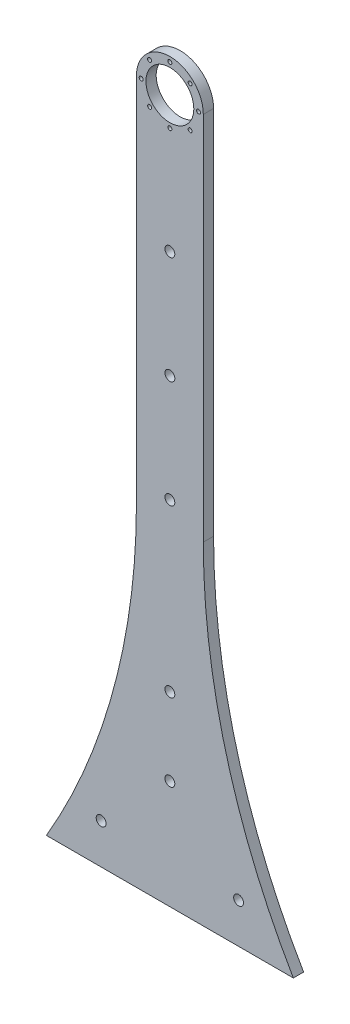
SolidWorks part; units mm, degrees
ref_plane "Front Plane" through (0, 0, 0) normal (0, 0, 1) x (1, 0, 0)
ref_plane "Top Plane" through (0, 0, 0) normal (0, 1, 0) x (1, 0, 0)
ref_plane "Right Plane" through (0, 0, 0) normal (1, 0, 0) x (0, 0, -1)
sketch "Sketch1" plane through (0, 0, 0) normal (0, 0, 1) x (1, 0, 0)
  line L0 (-112.3, 0) -> (112.3, 0) construction
  line L1 (-112.3, 0) -> (112.3, 0)
  line L2 (-29, 408.6) -> (29, 408.6) construction
  line L3 (-29, 408.6) -> (29, 408.6)
  line L4 (-31, 371.4) -> (-31, 408.6) construction
  line L5 (31, 408.6) -> (31, 371.4) construction
  line L6 (-31, 371.4) -> (-31, 408.6)
  line L7 (31, 408.6) -> (31, 371.4)
  line L8 (58.8, 370.05) -> (-58.8, 370.05) construction
  line L9 (58.8, 370.05) -> (-58.8, 370.05)
  line L10 (-125, 20) -> (125, 20) construction
  line L11 (-125, 20) -> (125, 20)
  line L12 (125, 0) -> (125, 10.5) construction
  line L13 (125, 0) -> (125, 10.5)
  line L14 (-125, 10.5) -> (-125, 0) construction
  line L15 (-125, 10.5) -> (-125, 0)
  circle A1 centre (0, 390) radius 8.5
  circle A2 centre (0, 390) radius 8.5
  circle A3 centre (0, 390) radius 3.025
  circle A4 centre (0, 390) radius 3.025
  dimension "D1" = 0
  dimension "D2" = 0
sketch "Sketch2" plane through (0, 0, 0) normal (0, 0, 1) x (1, 0, 0)
  line L0 (-29, 408.6) -> (29, 408.6) construction
  line L1 (-17.6, 390) -> (-17.6, 0) construction
  line L2 (-112.3, 0) -> (112.3, 0) construction
  line L3 (17.6, 390) -> (17.6, 0) construction
  line L4 (-65, 0) -> (65, 0) construction
  line L5 (-65, 0) -> (-65, 20) construction
  line L6 (-125, 20) -> (125, 20) construction
  line L7 (65, 0) -> (65, 20) construction
  line L8 (-125, 10.5) -> (-125, 0) construction
  line L9 (-17.6, 390) -> (-17.6, 195)
  line L10 (17.6, 390) -> (17.6, 195)
  line L11 (-65, 20) -> (65, 20)
  arc A0 (17.6, 390) -> (-17.6, 390) centre (0, 390) ccw
  circle A3 centre (0, 390) radius 12.6
  arc A4 (17.6, 195) -> (65, 20) centre (364.3485, 195) ccw
  arc A5 (-65, 20) -> (-17.6, 195) centre (-364.3485, 195) ccw
  point P3 (0, 407.6)
  point P13 (0, 0)
  point P30 (17.6, 195)
  dimension "D2" = 5
  dimension "D1" = 1
  dimension "D3" = 60
extrude "Boss-Extrude1" add sketch "Sketch2" against normal blind 5.4
sketch "Sketch3" plane through (0, 0, -5.4) normal (0, 0, -1) x (-1, 0, 0)
  line L0 (0, 407.6) -> (0, 402.6) construction
  arc A0 (17.6, 390) -> (-17.6, 390) centre (0, 390) ccw construction
  circle A1 centre (0, 390) radius 12.6 construction
  circle A2 centre (0, 405.1) radius 1.05
  circle A3 centre (10.6773, 400.6773) radius 1.05
  circle A4 centre (15.1, 390) radius 1.05
  circle A5 centre (10.6773, 379.3227) radius 1.05
  circle A6 centre (0, 374.9) radius 1.05
  circle A7 centre (-10.6773, 379.3227) radius 1.05
  circle A8 centre (-15.1, 390) radius 1.05
  circle A9 centre (-10.6773, 400.6773) radius 1.05
  circle A10 centre (0, 318.7) radius 2.1 construction
  circle A11 centre (0, 318.7) radius 2.1 construction
  circle A12 centre (0, 262.1) radius 2.1 construction
  circle A13 centre (0, 262.1) radius 2.1 construction
  circle A14 centre (0, 205.5) radius 2.1 construction
  circle A15 centre (0, 205.5) radius 2.1 construction
  circle A16 centre (0, 318.7) radius 2.6
  circle A17 centre (0, 117.9824) radius 2.1
  circle A18 centre (0, 117.9824) radius 2.1 construction
  circle A19 centre (0, 77.2624) radius 2.1
  circle A20 centre (0, 77.2624) radius 2.1 construction
  circle A21 centre (36.1749, 41.0875) radius 2.1
  circle A22 centre (36.1749, 41.0875) radius 2.1 construction
  circle A23 centre (-36.1749, 41.0875) radius 2.1
  circle A24 centre (-36.1749, 41.0875) radius 2.1 construction
  circle A25 centre (0, 262.1) radius 2.6
  circle A26 centre (0, 205.5) radius 2.6
  circle A27 centre (0, 117.9824) radius 2.6
  circle A28 centre (0, 77.2624) radius 2.6
  circle A29 centre (36.1749, 41.0875) radius 2.6
  circle A30 centre (-36.1749, 41.0875) radius 2.6
  point P10 (0, 390)
  dimension "D1" = 2.1
  dimension "D6" = 5.2
  dimension "D2" = 0
  dimension "D3" = 0
  dimension "D4" = 0
  dimension "D5" = 0
extrude "Cut-Extrude1" cut sketch "Sketch3" against normal through all
equation "\"Black_acrylic\"= 1.35mm"
equation "\"MDF_base\"= 20mm"
equation "\"Supports_material\"= 5.4mm"
equation "\"D1@Boss-Extrude1\"=\"Supports_material\""
